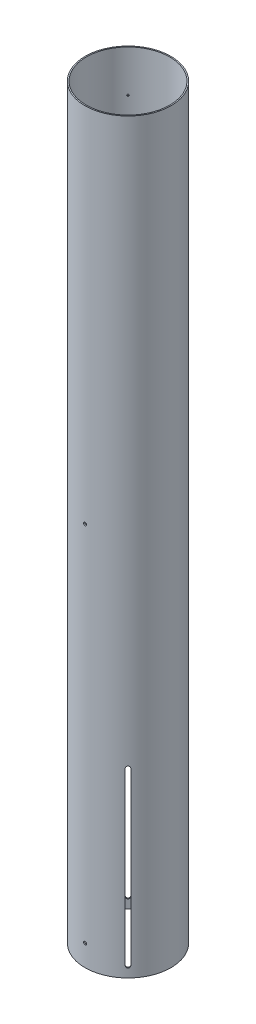
SolidWorks part; units mm, degrees
material "Wildman Fiberglass"
ref_plane "Front Plane" through (0, 0, 0) normal (0, 0, 1) x (1, 0, 0)
ref_plane "Top Plane" through (0, 0, 0) normal (0, 1, 0) x (1, 0, 0)
ref_plane "Right Plane" through (0, 0, 0) normal (1, 0, 0) x (0, 0, -1)
sketch "Sketch1" plane through (0, 0, 0) normal (0, 1, 0) x (1, 0, 0)
  circle A0 centre (0, 0) radius 49.657
  circle A1 centre (0, 0) radius 51.054
  dimension "D1" = 102.108
  dimension "D2" = 99.314
extrude "Boss-Extrude1" add sketch "Sketch1" along normal blind 887.984
extrude "Cut-Extrude1" cut sketch "Sketch2" against normal blind 152.4
sketch "Sketch2" plane through (14.4921, 1243.3556, -192.6285) normal (0.7071, 0, -0.7071) x (0, 1, 0)
  line L0 (-1230.6556, 128.3427) -> (-1027.4556, 128.3427)
  line L1 (-1027.4556, 123.5802) -> (-1230.6556, 123.5802)
  arc A0 (-1230.6556, 128.3427) -> (-1230.6556, 123.5802) centre (-1230.6556, 125.9615) ccw
  arc A1 (-1027.4556, 128.3427) -> (-1027.4556, 123.5802) centre (-1027.4556, 125.9615) cw
pattern_circular "CirPattern1" count 4 over 360 about axis through (0, 887.984, 0) along (0, -1, 0) of "Cut-Extrude1" reverse direction yes
extrude "Cut-Extrude2" cut sketch "Sketch3" against normal blind 11.684
sketch "Sketch3" plane through (271.0916, 1243.3556, 52.3875) normal (0, 0, 1) x (-1, 0, 0)
  circle A0 centre (271.0916, 1217.9556) radius 1.7653
  circle A2 centre (271.0916, 786.1556) radius 1.7653
extrude "Cut-Extrude3" cut sketch "Sketch4" against normal blind 25.4
sketch "Sketch4" plane through (120.5803, 708.4046, -48.7382) normal (0.7071, 0, 0.7071) x (-0.7071, 0, 0.7071)
  line L0 (68.9263, -129.7954) -> (170.5263, -129.7954) construction
  circle A0 centre (119.7263, -129.7954) radius 1.0922
pattern_circular "CirPattern2" count 2 over 360 about axis through (0, 887.984, 0) along (0, -1, 0) of "Cut-Extrude3"
equation "\"Length\"=34.96"
equation "\"D1@Boss-Extrude1\"=\"Length\""
